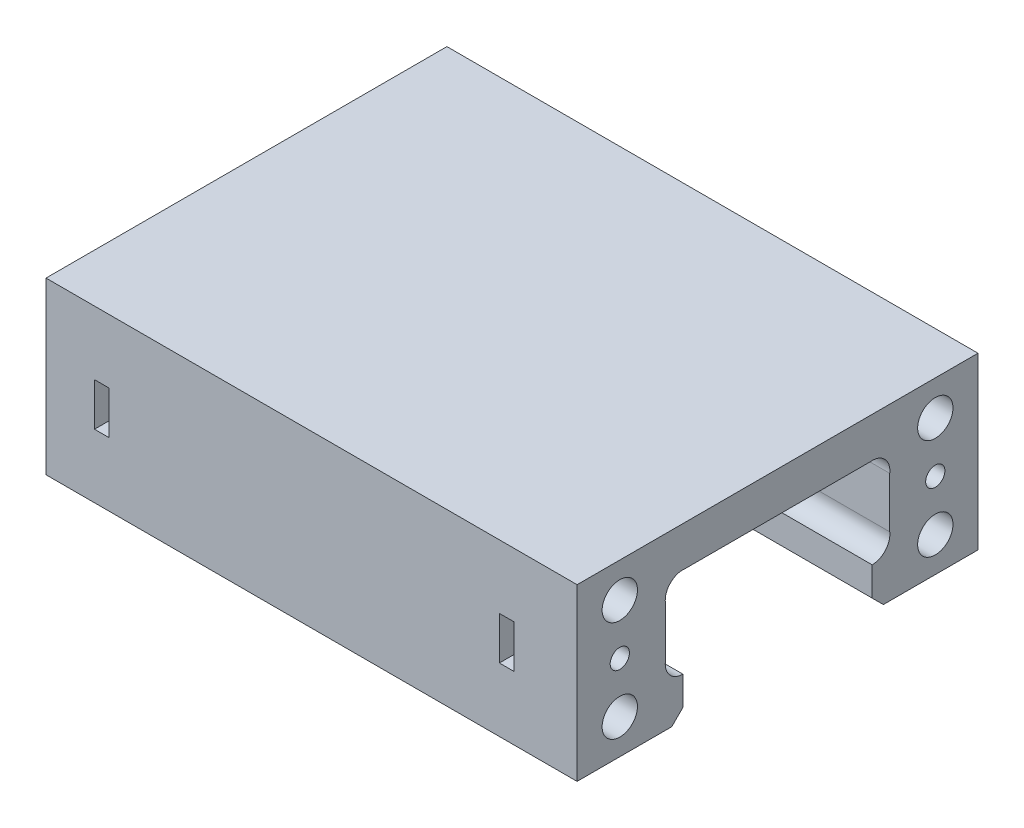
SolidWorks part; units mm, degrees
ref_plane "Front Plane" through (0, 0, 0) normal (0, 0, 1) x (1, 0, 0)
ref_plane "Top Plane" through (0, 0, 0) normal (0, 1, 0) x (1, 0, 0)
ref_plane "Right Plane" through (0, 0, 0) normal (1, 0, 0) x (0, 0, -1)
sketch "Sketch1" plane through (0, 0, 0) normal (1, 0, 0) x (0, 0, -1)
  line L0 (0, 0) -> (30, 0)
  line L1 (0, 0) -> (0, 5)
  line L2 (0, 5) -> (2.7781, 7.7781)
  line L3 (2.7781, 7.7781) -> (2.7781, 14.2781)
  line L4 (2.7781, 14.2781) -> (0, 14.2781) construction
  line L5 (0, 14.2781) -> (0, 23) construction
  line L6 (0, 23) -> (30, 23) construction
  line L12 (15, 0) -> (15, 23) construction
  line L13 (27.2219, 23) -> (2.7781, 23)
  line L14 (0, 20.2219) -> (0, 17.0562)
  line L15 (30, 14.2781) -> (30, 23) construction
  line L16 (27.2219, 14.2781) -> (30, 14.2781) construction
  line L17 (30, 20.2219) -> (30, 17.0562)
  line L18 (27.2219, 7.7781) -> (27.2219, 14.2781)
  line L19 (30, 5) -> (27.2219, 7.7781)
  line L20 (30, 0) -> (30, 5)
  arc A0 (2.7781, 14.2781) -> (0, 17.0562) centre (0, 14.2781) ccw
  arc A1 (0, 20.2219) -> (2.7781, 23) centre (0, 23) ccw
  arc A2 (30, 20.2219) -> (27.2219, 23) centre (30, 23) cw
  arc A3 (27.2219, 14.2781) -> (30, 17.0562) centre (30, 14.2781) cw
  dimension "D1" = 5.5563
  dimension "D2" = 15
  dimension "D3" = 23
  dimension "D4" = 45
  dimension "D5" = 6.5
  dimension "D6" = 5
sketch "Sketch2" plane through (0, 0, 0) normal (1, 0, 0) x (0, 0, -1)
  line L0 (-10, 26.6391) -> (-10, 32.1391) construction
  line L1 (15, 23) -> (15, -0.4684) construction
  line L2 (-10, 10.6391) -> (-10, 5.1391) construction
  line L3 (0, 25.7781) -> (30, 25.7781)
  line L4 (0, 11.5) -> (0, 6.9068)
  line L5 (0, 6.9068) -> (-1.7678, 5.1391)
  line L6 (-1.7678, 5.1391) -> (-16.7678, 5.1391)
  line L7 (-16.7678, 5.1391) -> (-16.7678, 32.1391)
  line L8 (-10, 26.6391) -> (0, 23) construction
  line L9 (0, 23) -> (0, 14.2781) construction
  line L10 (0, 14.2781) -> (-10, 10.6391) construction
  line L11 (-10, 10.6391) -> (-10, 26.6391) construction
  line L12 (0, 18.6391) -> (-10, 18.6391) construction
  line L13 (-16.7678, 32.1391) -> (46.7678, 32.1391)
  line L14 (15, 32.1391) -> (15, 25.7781) construction
  line L15 (-2.7781, 14.2781) -> (-2.7781, 23)
  line L16 (0, 5) -> (2.7781, 7.7781) construction
  line L17 (15, 0) -> (15, 23) construction
  line L18 (30, 18.6391) -> (40, 18.6391) construction
  line L19 (40, 10.6391) -> (40, 26.6391) construction
  line L20 (30, 14.2781) -> (40, 10.6391) construction
  line L21 (30, 23) -> (30, 14.2781) construction
  line L22 (40, 26.6391) -> (30, 23) construction
  line L23 (40, 10.6391) -> (40, 5.1391) construction
  line L24 (40, 26.6391) -> (40, 32.1391) construction
  line L25 (32.7781, 14.2781) -> (32.7781, 23)
  line L26 (46.7678, 5.1391) -> (46.7678, 32.1391)
  line L27 (31.7678, 5.1391) -> (46.7678, 5.1391)
  line L28 (30, 6.9068) -> (31.7678, 5.1391)
  line L29 (30, 11.5) -> (30, 6.9068)
  arc A0 (0, 25.7781) -> (-2.7781, 23) centre (0, 23) ccw
  arc A1 (-2.7781, 14.2781) -> (0, 11.5) centre (0, 14.2781) ccw
  arc A2 (2.7781, 14.2781) -> (0, 17.0562) centre (0, 14.2781) ccw construction
  circle A3 centre (-10, 26.6391) radius 2.7781
  circle A4 centre (-10, 10.6391) radius 2.7781
  circle A5 centre (40, 10.6391) radius 2.7781
  circle A6 centre (40, 26.6391) radius 2.7781
  arc A7 (32.7781, 14.2781) -> (30, 11.5) centre (30, 14.2781) cw
  arc A8 (30, 25.7781) -> (32.7781, 23) centre (30, 23) cw
  dimension "D1" = 10
  dimension "D2" = 16
  dimension "D3" = 15
  dimension "D4" = 27
  dimension "D5" = 2.5
extrude "Boss-Extrude2" add sketch "Sketch2" along normal blind 84.1648
sketch "Sketch3" plane through (84.1648, 0, 0) normal (1, 0, 0) x (0, 0, -1)
  line L0 (-10, 26.6391) -> (-10, 10.6391) construction
  line L1 (15, 20.921) -> (15, 13.7492) construction
  line L2 (15, 200023) -> (15, -200000.4684) construction
  line L3 (-10, 18.6391) -> (15, 18.6391) construction
  circle A0 centre (-10, 18.6391) radius 1.524
  circle A1 centre (40, 18.6391) radius 1.524
  dimension "D1" = 3.048
extrude "Cut-Extrude1" cut sketch "Sketch3" against normal blind 19.1668
ref_plane "Plane1" through (42.0824, 0, 0) normal (1, 0, 0) x (0, 0, -1)
mirror "Mirror1" about plane through (42.0824, 0, 0) normal (1, 0, 0) of "Cut-Extrude1"
ref_plane "Plane2" through (0, 18.6391, 0) normal (0, -1, 0) x (0, 0, -1)
ref_axis "Axis1" through (-32.539, 18.6391, 10) along (1, 0, 0)
ref_axis "Axis2" through (84.1648, 18.6391, -40) along (1, 0, 0)
sketch "Sketch4" plane through (0, 18.6391, 0) normal (0, -1, 0) x (0, 0, -1)
  line L0 (-16.7678, 84.1648) -> (-16.7678, 0) construction
  line L1 (-16.7678, 74.1648) -> (-6.9075, 74.1648)
  line L2 (-16.7678, 74.1648) -> (-16.7678, 71.8534)
  line L3 (-16.7678, 71.8534) -> (-6.9075, 71.8534)
  line L4 (-6.9075, 74.1648) -> (-6.9075, 71.8534)
  line L5 (46.7678, 84.1648) -> (46.7678, 0) construction
  line L6 (46.7678, 74.1648) -> (36.9075, 74.1648)
  line L7 (46.7678, 74.1648) -> (46.7678, 71.8534)
  line L8 (46.7678, 71.8534) -> (36.9075, 71.8534)
  line L9 (36.9075, 74.1648) -> (36.9075, 71.8534)
  line L10 (-16.7678, 84.1648) -> (-1.7678, 84.1648) construction
  line L11 (-16.7678, 7.6886) -> (-6.9075, 7.6886)
  line L12 (-16.7678, 7.6886) -> (-16.7678, 10)
  line L13 (-16.7678, 10) -> (-6.9075, 10)
  line L14 (-6.9075, 7.6886) -> (-6.9075, 10)
  line L15 (36.9075, 7.6886) -> (46.7678, 7.6886)
  line L16 (36.9075, 7.6886) -> (36.9075, 10)
  line L17 (36.9075, 10) -> (46.7678, 10)
  line L18 (46.7678, 7.6886) -> (46.7678, 10)
  line L19 (-16.7678, 0) -> (-1.7678, 0) construction
  point P24 (0, 0)
  dimension "D1" = 10
  dimension "D2" = 10
  dimension "D3" = 9.8602
  dimension "D4" = 2.3114
extrude "Cut-Extrude2" cut sketch "Sketch4" against normal mid plane 6.8072
sketch "Sketch5" plane through (84.1648, 0, 0) normal (1, 0, 0) x (0, 0, -1)
  circle A0 centre (-10, 26.6391) radius 2.8
  circle A1 centre (0, 23) radius 2.8
  circle A2 centre (-10, 10.6391) radius 2.8
  circle A3 centre (40, 26.6391) radius 2.8
  circle A4 centre (40, 10.6391) radius 2.8
  circle A5 centre (30, 23) radius 2.8
  circle A6 centre (0, 14.2781) radius 2.8
  circle A7 centre (30, 14.2781) radius 2.8
  arc A8 (0, 25.7781) -> (-2.7781, 23) centre (0, 23) ccw construction
  arc A9 (-2.7781, 14.2781) -> (0, 11.5) centre (0, 14.2781) ccw construction
  arc A10 (30, 11.5) -> (32.7781, 14.2781) centre (30, 14.2781) ccw construction
  arc A11 (32.7781, 23) -> (30, 25.7781) centre (30, 23) ccw construction
  dimension "D1" = 5.6
extrude "Cut-Extrude3" cut sketch "Sketch5" against normal through all
